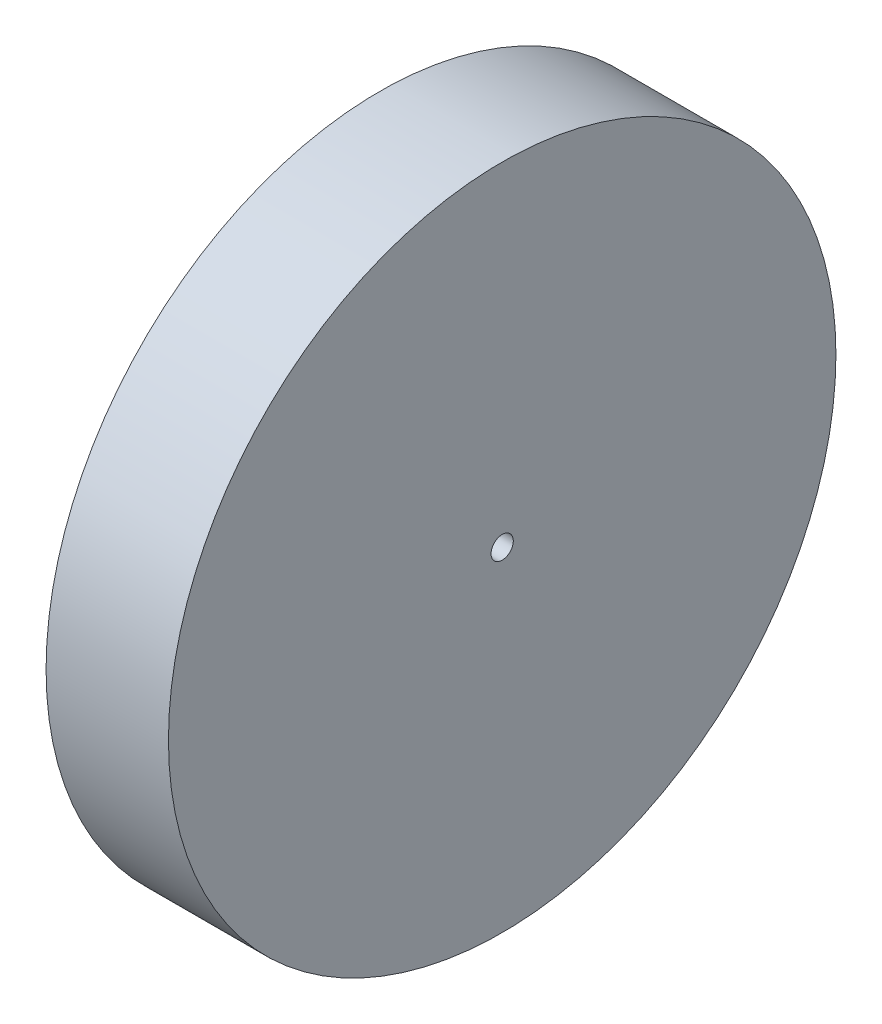
SolidWorks part; units mm, degrees
ref_plane "Plane1" through (0, 0, 0) normal (0, 0, 1) x (1, 0, 0)
ref_plane "Plane2" through (0, 0, 0) normal (0, 1, 0) x (1, 0, 0)
ref_plane "Plane3" through (0, 0, 0) normal (1, 0, 0) x (0, 0, -1)
sketch "HoldingSke" plane through (0, 0, 0) normal (0, 1, 0) x (1, 0, 0)
  line L0 (0, 0) -> (0.3214, -0.383)
  line L1 (-15, 0) -> (100, 0) construction
  line L2 (0, 0) -> (-2.1039, 2.3779)
  line L3 (0, 0) -> (-11.863, 4.5341)
  line L4 (0, 0) -> (5.5511, 6.6156)
  line L5 (0, 0) -> (-23.7986, -8.8762)
  line L6 (0, 0) -> (-10.5278, -7.1032)
  line L7 (-2.1039, 2.3779) -> (3.3635, 27.1825)
  line L8 (-76.2, 4.3779) -> (-54.61, 4.3779)
  line L9 (-71.009, 38.7566) -> (-53.1078, 45.2721)
  line L10 (-76.2, 71.12) -> (104.1128, 71.12)
  line L11 (0, 0) -> (-12, 0)
  line L12 (-76.2, 101.6) -> (-76.133, 101.6)
  line L13 (24.9733, 27.94) -> (52.9518, 28.4284)
  line L14 (24.9733, 27.94) -> (24.9743, 27.94)
  line L15 (24.9733, 27.94) -> (100.4006, 29.5858)
  circle A0 centre (0, 0) radius 60
  circle A1 centre (0, 0) radius 12.7
  circle A2 centre (0, 0) radius 12.7
  dimension "MHD" = 25.4
  dimension "Hub_dia" = 25.4
  dimension "Diameter" = 120
  dimension "Num_teeth" = 50
  dimension "Pitch_radius" = 180.3128
  dimension "Pitch" = 0.5
  dimension "Width" = 12
  dimension "Overall_len" = 25.4
  dimension "Show_teeth" = 50
  dimension "Thickness" = 12.7
  dimension "OAL" = 25.4001
  dimension "T_dim" = 21.59
  dimension "Ap" = 20
  dimension "H" = 19.05
  dimension "Backlash" = 0.067
  dimension "Addendum_fac" = 1
  dimension "Dedendum_fac" = 1.25
  dimension "Clearance_fac" = 0.25
  dimension "Dedendum_add" = 0.001
  dimension "Module" = 2
sketch "BasProSke" plane through (0, 0, 0) normal (0, 1, 0) x (1, 0, 0)
  line L0 (-10, 0) -> (60, 0) construction
  line L1 (0, 48) -> (0, 60)
  line L2 (0, 48) -> (12, 48)
  line L3 (12, 48) -> (12, 60)
  line L4 (12, 60) -> (0, 60)
  dimension "Diameter" = 120
  dimension "Thickness" = 12
  dimension "Inside_diameter" = 96
revolve "Base-Revolve" add sketch "BasProSke" angle 360 about L0
sketch "TooCutSke" plane through (0, 0, 0) normal (1, 0, 0) x (0, 0, -1)
  line L3 (1.738, 49.9698) -> (1.738, 53.6633) construction
  line L4 (0, 0) -> (0, 59.563) construction
  line L5 (0, 0) -> (-4.2903, 68.1927) construction
  line L6 (-21.6015, 41.0107) -> (35.113, 44.5789) construction
  circle A0 centre (0, 0) radius 50 construction
  circle A1 centre (0, 0) radius 52.501 construction
  circle A2 centre (0, 0) radius 42.2862 construction
  circle A3 centre (0, 0) radius 47.9746 construction
  arc A4 (2.4267, 47.9132) -> (0.6033, 52.4975) centre (-21.6015, 41.0107) ccw
  arc A5 (2.4267, 47.9132) -> (-2.4267, 47.9132) centre (0, 0) ccw
  arc A6 (0.6033, 52.4975) -> (-0.6033, 52.4975) centre (0, 0) ccw
  arc A7 (-0.6033, 52.4975) -> (-2.4267, 47.9132) centre (21.6015, 41.0107) ccw
  dimension "Pitch_dia" = 100
  dimension "Base_dia" = 84.5723
  dimension "Root_dia" = 105.002
  dimension "Overcut_dia" = 95.9492
  dimension "Flank_rad" = 25
  dimension "Half_ang" = 3.6
  dimension "Half_CT" = 1.738
extrude "ToothCut" cut sketch "TooCutSke" along normal through all
fillet "Breaks" [suppressed] radius 0.2
fillet "RootFillets" [suppressed] radius 0.501
pattern_circular "TeethCuts" count 50 over 360 about axis through (-10, 0, 0) along (1, 0, 0) of "RootFillets", "Breaks", "ToothCut"
sketch "Esquisse1" plane through (12, 0, 0) normal (1, 0, 0) x (0, 0, -1)
  circle A0 centre (0, 0) radius 60
  circle A1 centre (0, 0) radius 2
  dimension "D1" = 120
  dimension "D2" = 4
extrude "Boss.-Extru.1" add sketch "Esquisse1" along normal blind 10
ref_axis "Axe1" through (22, 0, 0) along (-1, 0, 0)
equation "' \"Module@HoldingSke\" = 6.35"
equation "' \"Num_teeth@HoldingSke\" = 24"
equation "' \"Ap@HoldingSke\" =  14.5"
equation "' \"Width@HoldingSke\" = 12"
equation "' \"Diameter@HoldingSke\" = 8 * 25.4"
equation "' \"Show_teeth@HoldingSke\" = 100"
equation "' \"Backlash@HoldingSke\" = 0.009 * 25.4"
equation "' \"Addendum_fac@HoldingSke\" = 1.0"
equation "' \"Dedendum_fac@HoldingSke\" = 1.25"
equation "' \"Dedendum_add@HoldingSke\" = 0.00005 * 25.4"
equation "' \"Clearance_fac@HoldingSke\" = 0.25"
equation "\"Pitch@HoldingSke\" = 1 / \"Module@HoldingSke\" "
equation "\"Overcut_dia@TooCutSke\" = (\"Num_teeth@HoldingSke\" - 2 * \"Addendum_fac@HoldingSke\") / \"Pitch@HoldingSke\" - 0.002 * 25.4"
equation "\"Pitch_dia@TooCutSke\" = \"Num_teeth@HoldingSke\" / \"Pitch@HoldingSke\""
equation "\"Base_dia@TooCutSke\" = \"Num_teeth@HoldingSke\" / \"Pitch@HoldingSke\" * cos((\"Ap@HoldingSke\"  * 3.14159265 / 180)) * 0.90"
equation "\"Root_dia@TooCutSke\" = \"Num_teeth@HoldingSke\"  / \"Pitch@HoldingSke\" + 2 *  \"Dedendum_fac@HoldingSke\"/ \"Pitch@HoldingSke\" + \"Dedendum_add@HoldingSke\" * 2"
equation "\"Half_ang@TooCutSke\" = 180 / \"Num_teeth@HoldingSke\""
equation "\"Half_CT@TooCutSke\" = \"Num_teeth@HoldingSke\" / \"Pitch@HoldingSke\" * sin((3.14159265 / 2 / \"Num_teeth@HoldingSke\")) / 2 + 10 * \"Backlash@HoldingSke\" / 4"
equation "\"Flank_rad@TooCutSke\" = \"Num_teeth@HoldingSke\" / \"Pitch@HoldingSke\" / 4"
equation "\"Radius@RootFillets\"= \"Clearance_fac@HoldingSke\" / \"Pitch@HoldingSke\" + \"Dedendum_add@HoldingSke\""
equation "\"Break_rad@Breaks\" = 0.02 / \"Pitch@HoldingSke\" * 5"
equation "\"Num_teeth@TeethCuts\" = int( \"Show_teeth@HoldingSke\" ) + 1"
equation "\"Num_teeth@TeethCuts\" = ((sgn( \"Num_teeth@TeethCuts\" - \"Num_teeth@HoldingSke\" )-1)*( \"Num_teeth@TeethCuts\" - \"Num_teeth@HoldingSke\" ))/-2+ \"Num_teeth@HoldingSke\""
equation "\"Num_teeth@TeethCuts\" = ((sgn( \"Num_teeth@TeethCuts\" - 2.0)+1)*( \"Num_teeth@TeethCuts\" - 2.0))/2 +2.0"
equation "\"Angle@TeethCuts\" = 360.0 / \"Num_teeth@HoldingSke\""
equation "\"Diameter@BasProSke\" = \"Num_teeth@HoldingSke\"  / \"Pitch@HoldingSke\" + 2 *  \"Dedendum_fac@HoldingSke\"/ \"Pitch@HoldingSke\" + \"Dedendum_add@HoldingSke\" * 2 + 0.002 * 25.4"
equation "\"Diameter@BasProSke\" = ((sgn( \"Diameter@BasProSke\"  - \"Diameter@HoldingSke\" )+1)*( \"Diameter@BasProSke\"  - \"Diameter@HoldingSke\" ))/2 + \"Diameter@HoldingSke\""
equation "\"Inside_diameter@BasProSke\" =  (\"Num_teeth@HoldingSke\" - 2 * \"Addendum_fac@HoldingSke\") / \"Pitch@HoldingSke\" "
equation "\"Thickness@BasProSke\"  = \"Width@HoldingSke\""
